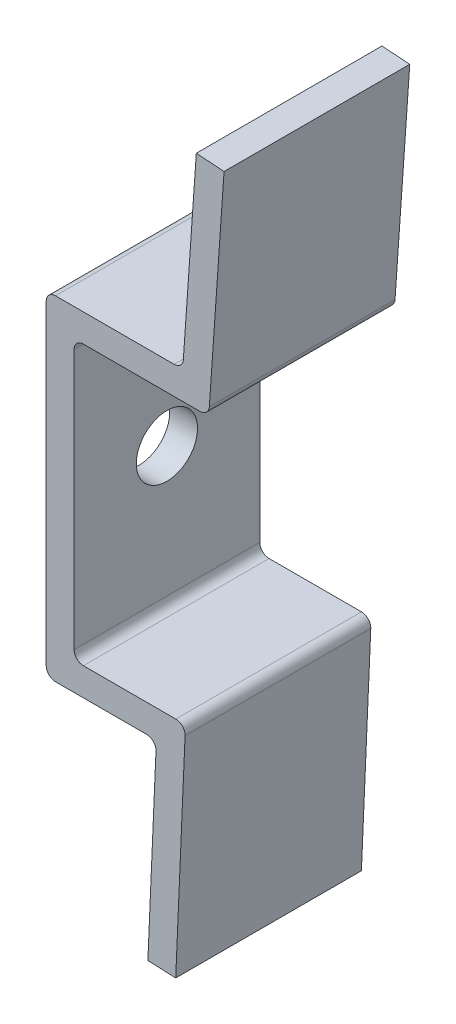
SolidWorks part; units mm, degrees
ref_plane "Спереди" through (0, 0, 0) normal (0, 0, 1) x (1, 0, 0)
ref_plane "Сверху" through (0, 0, 0) normal (0, 1, 0) x (1, 0, 0)
ref_plane "Справа" through (0, 0, 0) normal (1, 0, 0) x (0, 0, -1)
sketch "Эскиз1" plane through (0, 0, 0) normal (0, 0, 1) x (1, 0, 0)
  line L0 (0, 17) -> (0, -17)
  line L1 (1, -18) -> (10.8215, -18)
  line L2 (11.8206, -19.0436) -> (10.9482, -39.0246)
  line L3 (10.9482, -39.0246) -> (13.9454, -39.1554)
  line L4 (13.9454, -39.1554) -> (14.9544, -16.0436)
  line L5 (13.9554, -15) -> (4, -15)
  line L6 (3, -14) -> (3, 14)
  line L7 (4, 15) -> (16.5675, 15)
  line L8 (17.565, 15.9302) -> (19.1553, 38.6723)
  line L9 (19.1553, 38.6723) -> (16.1626, 38.8815)
  line L12 (16.1626, 38.8815) -> (14.7675, 18.9302)
  line L13 (13.7699, 18) -> (1, 18)
  arc A0 (14.7675, 18.9302) -> (13.7699, 18) centre (13.7699, 19) cw
  arc A1 (16.5675, 15) -> (17.565, 15.9302) centre (16.5675, 16) ccw
  arc A2 (14.9544, -16.0436) -> (13.9554, -15) centre (13.9554, -16) ccw
  arc A3 (10.8215, -18) -> (11.8206, -19.0436) centre (10.8215, -19) cw
  arc A4 (0, -17) -> (1, -18) centre (1, -17) ccw
  arc A5 (4, -15) -> (3, -14) centre (4, -14) cw
  arc A6 (3, 14) -> (4, 15) centre (4, 14) cw
  arc A7 (0, 17) -> (1, 18) centre (1, 17) cw
  point P17 (17.5, 15)
  point P20 (15, -15)
  point P29 (3, 15)
  dimension "D12" = 1
  dimension "D1" = 3
  dimension "D2" = 3
  dimension "D3" = 3
  dimension "D4" = 30
  dimension "D5" = 15
  dimension "D6" = 3
  dimension "D7" = 3
  dimension "D8" = 94
  dimension "D9" = 12
  dimension "D10" = 14.5
  dimension "D11" = 87.5
  dimension "D13" = 20
  dimension "D14" = 20
extrude "Бобышка-Вытянуть1" add sketch "Эскиз1" along normal blind 10 and the other way blind 10
hole_wizard "Отверстие с зазором M61" positions "Трехмерный эскиз1" profile "Эскиз2" hole size "M6" standard "ISO" end condition through all
sketch3d "Трехмерный эскиз1"
  point P11 (0, 0, 0)
sketch "Эскиз2" plane through (0, 0, 0) normal (0, 1, 0) x (0, 0, 1)
  line L0 (0, 0) -> (0, 19.1553)
  line L1 (0, 19.1553) -> (3.3, 19.1553)
  line L2 (3.3, 19.1553) -> (3.3, 0)
  line L5 (3.3, 0) -> (0, 0)
  line L11 (0, -6.35) -> (0, 107.95) construction
  dimension "Диаметр сквозного отверстия" = 6.6
  dimension "Глубина сквозного отверстия" = 19.1553
